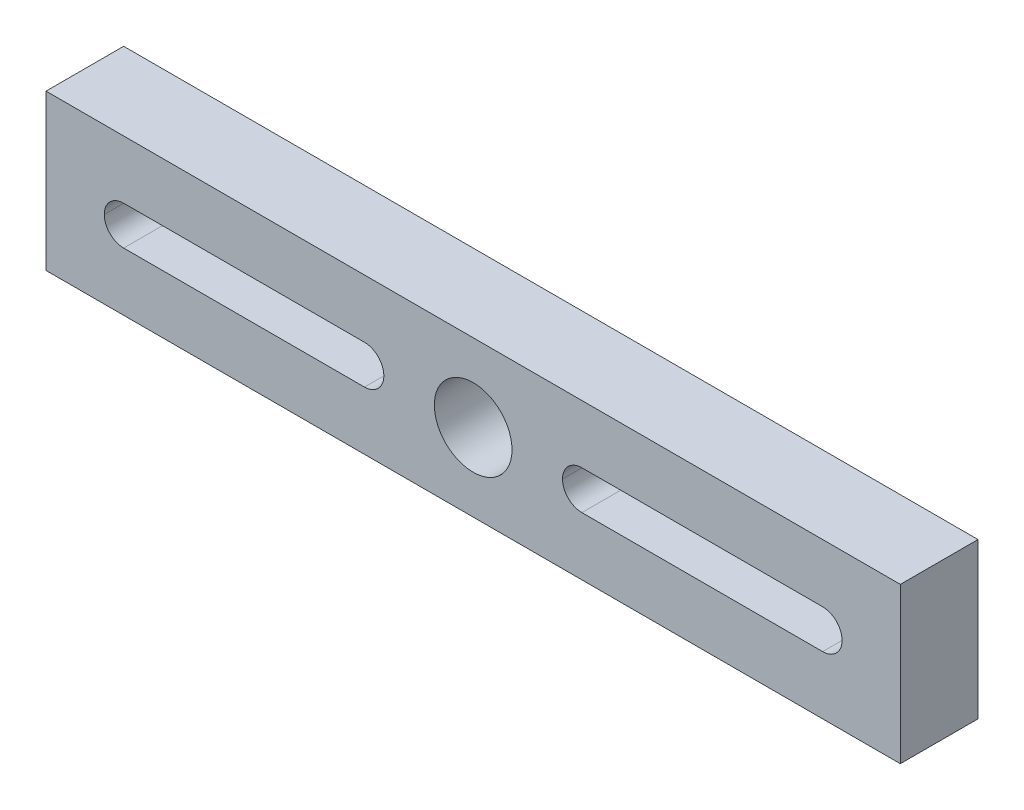
SolidWorks part; units mm, degrees
material "1060 Alloy"
ref_plane "Front Plane" through (0, 0, 0) normal (0, 0, 1) x (1, 0, 0)
ref_plane "Top Plane" through (0, 0, 0) normal (0, 1, 0) x (1, 0, 0)
ref_plane "Right Plane" through (0, 0, 0) normal (1, 0, 0) x (0, 0, -1)
sketch "Sketch1" plane through (0, 0, 0) normal (0, 0, 1) x (1, 0, 0)
  line L0 (55, 0) -> (-55, 0) construction
  line L1 (-69.85, 12.7) -> (69.85, 12.7)
  line L2 (-69.85, 12.7) -> (-69.85, -12.7)
  line L3 (-69.85, -12.7) -> (69.85, -12.7)
  line L4 (69.85, 12.7) -> (69.85, -12.7)
  line L5 (0, -55) -> (0, 55) construction
  circle A0 centre (0, 0) radius 6.35
  dimension "D1" = 12.7
  dimension "D2" = 25.4
  dimension "D3" = 12.7
  dimension "D4" = 139.7
  dimension "D5" = 69.85
extrude "Boss-Extrude1" add sketch "Sketch1" along normal blind 12.7
sketch "Sketch3" plane through (0, 12.7, 0) normal (0, 1, 0) x (1, 0, 0)
  circle A0 centre (17.9517, -6.9968) radius 2.032
  circle A1 centre (43.3517, -6.9968) radius 2.032
  dimension "D1" = 4.064
  dimension "D2" = 4.064
  dimension "D3" = 25.4
sketch "Sketch4" plane through (0, 0, 12.7) normal (0, 0, 1) x (1, 0, 0)
  line L0 (-69.85, 12.7) -> (-69.85, -12.7) construction
  line L1 (-60.325, 3.175) -> (-14.605, 3.175)
  line L2 (-60.325, 3.175) -> (-60.325, -3.175)
  line L3 (-60.325, -3.175) -> (-14.605, -3.175)
  line L4 (-14.605, 3.175) -> (-14.605, -3.175)
  line L5 (-69.85, -12.7) -> (69.85, -12.7) construction
  line L6 (69.85, 12.7) -> (-69.85, 12.7) construction
  line L7 (0, -6.985) -> (0, 6.985) construction
  line L8 (14.605, 3.175) -> (14.605, -3.175)
  line L9 (60.325, -3.175) -> (14.605, -3.175)
  line L10 (60.325, 3.175) -> (60.325, -3.175)
  line L11 (60.325, 3.175) -> (14.605, 3.175)
  dimension "D1" = 9.525
  dimension "D2" = 9.525
  dimension "D3" = 9.525
  dimension "D4" = 45.72
extrude "Cut-Extrude1" cut sketch "Sketch4" against normal blind 13.335
ref_plane "Plane1" [suppressed] through (0, 0, 6.35) normal (0, 0, 1) x (1, 0, 0)
mirror "Mirror1" [suppressed] about plane through (0, 0, 6.35) normal (0, 0, 1)
fillet "Fillet1" radius 3.175 8 edges at (-14.605, 3.175, 6.35) (-14.605, -3.175, 6.35) (-60.325, -3.175, 6.35) (-60.325, 3.175, 6.35) (14.605, 3.175, 6.35) (14.605, -3.175, 6.35) (60.325, -3.175, 6.35) (60.325, 3.175, 6.35)
